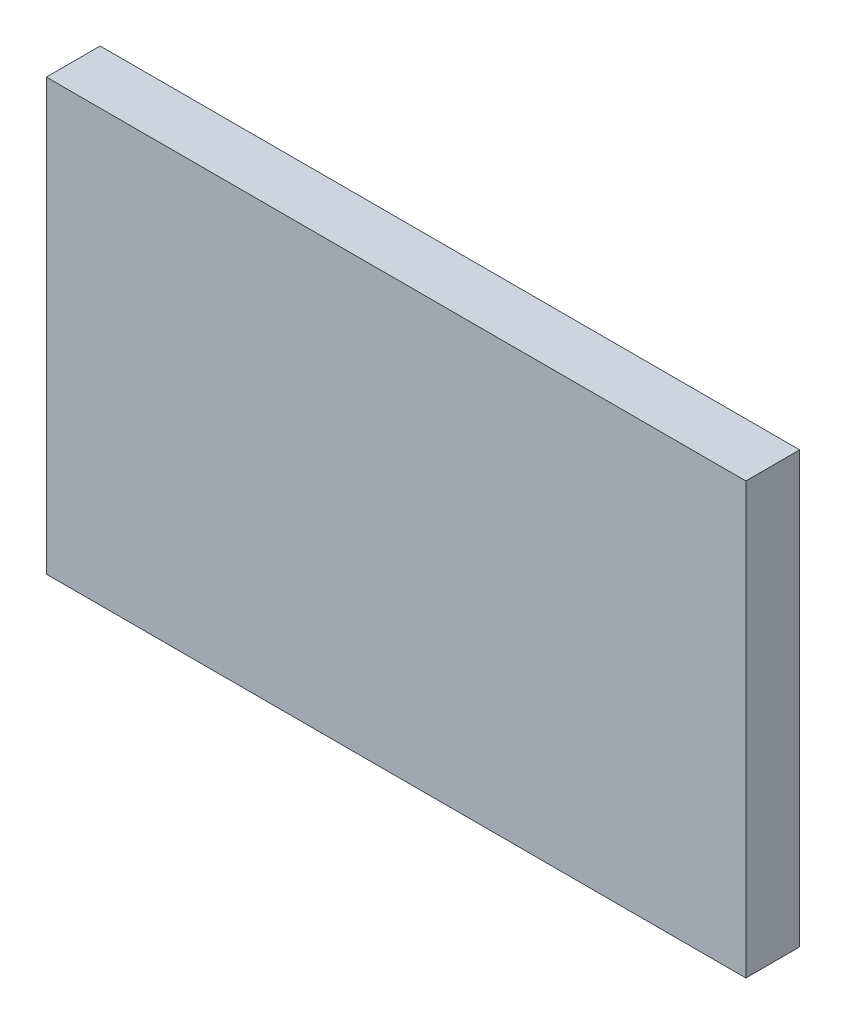
SolidWorks part; units mm, degrees
ref_plane "Front Plane" through (0, 0, 0) normal (0, 0, 1) x (1, 0, 0)
ref_plane "Top Plane" through (0, 0, 0) normal (0, 1, 0) x (1, 0, 0)
ref_plane "Right Plane" through (0, 0, 0) normal (1, 0, 0) x (0, 0, -1)
sketch "Sketch1" plane through (0, 0, 0) normal (0, 0, 1) x (1, 0, 0)
  line L1 (-7.5, 10) -> (7.5, 10)
  line L2 (-7.5, 10) -> (-7.5, -10)
  line L3 (-7.5, -10) -> (7.5, -10)
  line L4 (7.5, 10) -> (7.5, -10)
  line L5 (-7.5, 10) -> (7.5, -10) construction
  line L6 (-7.5, -10) -> (7.5, 10) construction
  point P0 (0, 0)
  dimension "D1" = 15
  dimension "D2" = 20
extrude "Boss-Extrude1" add sketch "Sketch1" along normal blind 230
sketch "Sketch2" plane through (0, 0, 0) normal (0, 0, -1) x (-1, 0, 0)
  line L1 (-32.5, 10) -> (32.5, 10)
  line L2 (-32.5, 10) -> (-32.5, 50)
  line L3 (-32.5, 50) -> (32.5, 50)
  line L4 (32.5, 10) -> (32.5, 50)
  line L6 (-7.5, 10) -> (7.5, 10) construction
  point P4 (0, 10)
  point P10 (0, 10)
  dimension "D1" = 65
  dimension "D2" = 40
extrude "Boss-Extrude6" add sketch "Sketch2" against normal blind 5 separate body
sketch "Sketch7" plane through (32.5, 0, 0) normal (1, 0, 0) x (0, 0, -1)
  line L0 (0, 50) -> (0, 10) construction
  line L1 (0, 37.5) -> (-75, 37.5)
  line L2 (0, 37.5) -> (0, 22.5)
  line L3 (0, 22.5) -> (-75, 22.5)
  line L4 (-75, 37.5) -> (-75, 22.5)
  point P4 (0, 30)
  point P7 (0, 30)
  dimension "D1" = 15
  dimension "D2" = 75
extrude "Boss-Extrude7" add sketch "Sketch7" along normal blind 5 separate body
sketch "Sketch8" plane through (-32.5, 0, 0) normal (-1, 0, 0) x (0, 0, 1)
  line L1 (0, 37.5) -> (75, 37.5)
  line L2 (0, 37.5) -> (0, 22.5)
  line L3 (0, 22.5) -> (75, 22.5)
  line L4 (75, 37.5) -> (75, 22.5)
extrude "Boss-Extrude8" add sketch "Sketch8" along normal blind 5 separate body
sketch "Sketch9" plane through (0, 0, 75) normal (0, 0, 1) x (1, 0, 0)
  line L1 (-32.5, 50) -> (32.5, 50)
  line L2 (-32.5, 50) -> (-32.5, 10)
  line L3 (-32.5, 10) -> (32.5, 10)
  line L4 (32.5, 50) -> (32.5, 10)
extrude "Boss-Extrude11" add sketch "Sketch9" against normal blind 5 separate body
sketch "Sketch10" plane through (-7.5, 0, 0) normal (-1, 0, 0) x (0, 0, 1)
  line L0 (230, 10) -> (230, -10) construction
  line L2 (209.8431, 2) -> (211.3431, 2)
  line L3 (209.8431, 2) -> (209.8431, -2)
  line L4 (209.8431, -2) -> (211.3431, -2)
  line L6 (209.8431, 2) -> (211, 0) construction
  line L7 (209.8431, -2) -> (211, 0) construction
  arc A0 (211.3431, -2) -> (211.3431, 2) centre (217, 0) ccw
  point P4 (230, 0)
  point P5 (211, 0)
  point P11 (209.8431, 0)
  dimension "D1" = 12
  dimension "D2" = 13
  dimension "D3" = 1.5
  dimension "D4" = 4
extrude "Cut-Extrude1" cut sketch "Sketch10" against normal through all
delete or keep bodies "Body-Delete/Keep 2" type delete bodies bodies 108 109 110 107
